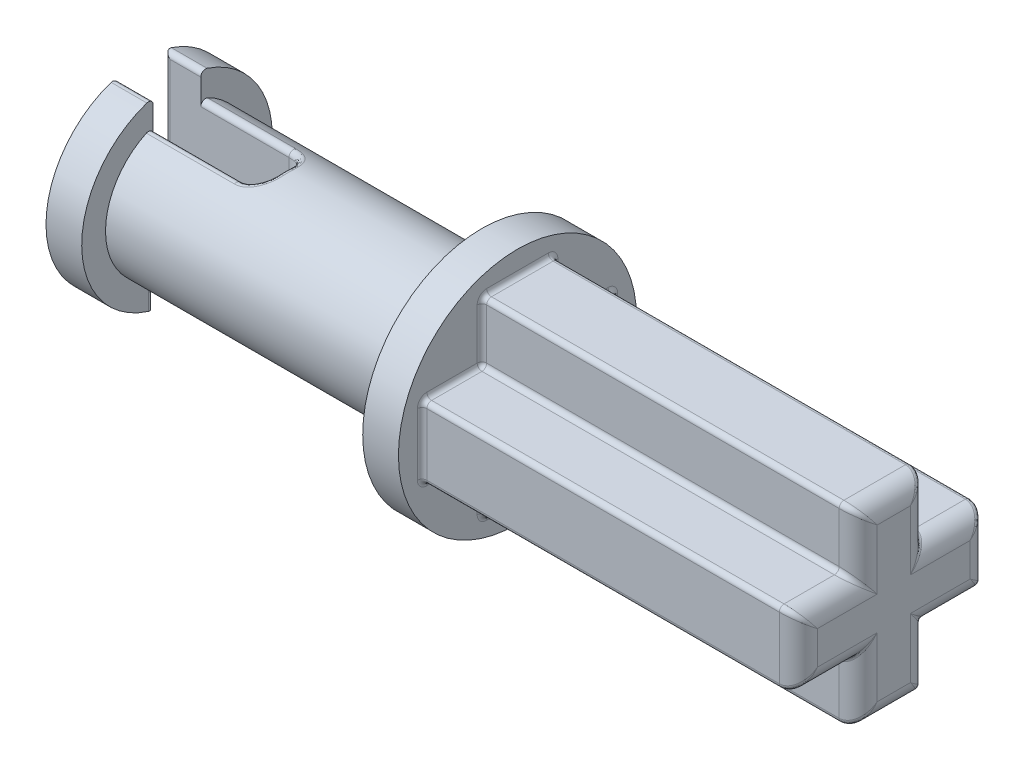
SolidWorks part; units mm, degrees
ref_plane "Front Plane" through (0, 0, 0) normal (0, 0, 1) x (1, 0, 0)
ref_plane "Top Plane" through (0, 0, 0) normal (0, 1, 0) x (1, 0, 0)
ref_plane "Right Plane" through (0, 0, 0) normal (1, 0, 0) x (0, 0, -1)
sketch "CircularBase" plane through (0, 0, 0) normal (0, 0, 1) x (1, 0, 0)
  line L0 (-5.0594, 0) -> (7.0797, 0) construction
  line L1 (0, 0) -> (0, 0.5)
  line L2 (0, 0.5) -> (-2, 0.5)
  line L3 (-2, 0.5) -> (-2, 2)
  line L4 (-2, 2) -> (-1.25, 2)
  line L5 (-1.25, 2) -> (-1.25, 1.5)
  line L6 (-1.25, 1.5) -> (5.15, 1.5)
  line L7 (5.15, 1.5) -> (5.15, 2.5)
  line L8 (5.15, 2.5) -> (5.9, 2.5)
  line L9 (5.9, 2.5) -> (5.9, 0)
  line L11 (0, 0) -> (5.9, 0)
  line L12 (7.0797, 0) -> (14.1483, 0) construction
  dimension "D1" = 0.75
  dimension "D2" = 0.75
  dimension "D3" = 1
  dimension "D4" = 0.5
  dimension "D5" = 1.5
  dimension "D6" = 0.5
  dimension "D7" = 2.5
  dimension "D8" = 2
  dimension "D9" = 5.9
revolve "CircularBaseRevolve" add sketch "CircularBase" angle 360 about L12
ref_plane "BasePlane" through (-2, 0, 0) normal (-1, 0, 0) x (0, 0, 1)
sketch "NotchCutSketc" plane through (-2, 0, 0) normal (-1, 0, 0) x (0, 0, 1)
  line L0 (0, 2) -> (0, -2) construction
  line L1 (-0.5, 0) -> (-0.5, 1.9365)
  line L2 (-0.5, 1.9365) -> (0.5, 1.9365)
  line L3 (-0.5, 0) -> (-0.5, -1.9365)
  line L4 (-0.5, -1.9365) -> (0.5, -1.9365)
  line L5 (0.5, 0) -> (0.5, -1.9365)
  line L6 (0.5, 0) -> (0.5, 1.9365)
  circle A0 centre (0, 0) radius 2 construction
  circle A1 centre (0, 0) radius 0.5 construction
  circle A2 centre (0, 0) radius 0.5 construction
  point P15 (0, -1.9365)
  point P17 (0, 1.9365)
extrude "NotchCut" cut sketch "NotchCutSketc" against normal blind 3
fillet "InsideNotchFillet1" radius 0.4 1 edges at (1, 0, -0.5) type face fillet first side face at (-0.875, 0, -0.5) second side face at (1, 0, 0)
fillet "InsideNotchFillet2" radius 0.4 1 edges at (1, 0, 0.5) type face fillet first side face at (-0.875, 0, 0.5) second side face at (1, 0, 0.2021)
fillet "OutsideNotchFillet" radius 0.1 16 edges at (-2, 0, 0.5) (-2, 0, -0.5) (-0.325, -1.4142, -0.5) (0.915, -1.4594, -0.3465) (1, -1.5, 0) (0.8413, -1.4403, 0.419) (-0.325, 1.4142, 0.5) (0.915, 1.4594, 0.3465) (1, 1.5, 0) (0.8413, 1.4403, -0.419) (-1.625, 1.9365, 0.5) (-1.625, 1.9365, -0.5) (-1.625, -1.9365, -0.5) (-0.325, -1.4142, 0.5) (-0.325, 1.4142, -0.5) (-1.25, -1.6754, 0.5)
ref_plane "TopBasePlane" through (5.9, 0, 0) normal (1, 0, 0) x (0, 0, -1)
sketch "TopCircularBaseExtrudeSketch" plane through (5.9, 0, 0) normal (1, 0, 0) x (0, 0, -1)
  line L0 (0, 2.007) -> (0, -2.007) construction
  line L13 (-2.0033, 0) -> (2.0033, 0) construction
  line L16 (-2.0033, -0.7505) -> (-2.0033, 0.7505)
  line L17 (-2.0033, 0.7505) -> (-0.7468, 0.7505)
  line L18 (0.7468, 2.007) -> (-0.7468, 2.007)
  line L19 (-0.7468, 2.007) -> (-0.7468, 0.7505)
  line L20 (2.0033, -0.7505) -> (2.0033, 0.7505)
  line L21 (2.0033, 0.7505) -> (0.7468, 0.7505)
  line L22 (0.7468, 2.007) -> (0.7468, 0.7505)
  line L23 (2.0033, -0.7505) -> (0.7468, -0.7505)
  line L24 (0.7468, -2.007) -> (0.7468, -0.7505)
  line L25 (-2.0033, -0.7505) -> (-0.7468, -0.7505)
  line L26 (-0.7468, -2.007) -> (-0.7468, -0.7505)
  line L27 (0.7468, -2.007) -> (-0.7468, -2.007)
  point P16 (2.0033, 0)
extrude "TopCircularBaseExtrude" add sketch "TopCircularBaseExtrudeSketch" along normal blind 7.9
fillet "TopCircularBaseFillet" radius 0.4 12 edges at (13.8, 1.3788, 0.7468) (13.8, 1.3788, -0.7468) (13.8, 0.7505, 1.375) (13.8, 0.7505, -1.375) (13.8, 0, -2.0033) (13.8, -0.7505, -1.375) (13.8, -1.3788, -0.7468) (13.8, -2.007, 0) (13.8, 0, 2.0033) (13.8, 2.007, 0) (13.8, -0.7505, 1.375) (13.8, -1.3788, 0.7468)
fillet "TopCircularbaseSideFillet" radius 0.1 36 edges at (5.9, 1.3788, 0.7468) (5.9, -2.007, 0) (5.9, -0.7505, -1.375) (5.9, 0.7505, -1.375) (5.9, 2.007, 0) (5.9, 0.7505, 1.375) (5.9, -0.7505, 1.375) (13.6828, -1.8899, -0.6296) (13.6828, -0.6334, -0.6296) (13.6828, -0.6334, 0.6296) (13.6828, -1.8899, 0.6296) (13.6828, -0.6334, -1.8861) (13.6828, 0.6334, -1.8861) (13.6828, 0.6334, -0.6296) (13.6828, 1.8899, -0.6296) (13.6828, 0.6334, 1.8861) (13.6828, 0.6334, 0.6296) (13.6828, 1.8899, 0.6296) (13.6828, -0.6334, 1.8861) (5.9, -1.3788, -0.7468) (9.65, -2.007, -0.7468) (9.65, -0.7505, -0.7468) (5.9, -1.3788, 0.7468) (9.65, -0.7505, 0.7468) (9.65, -2.007, 0.7468) (5.9, 0, -2.0033) (9.65, -0.7505, -2.0033) (9.65, 0.7505, -2.0033) (5.9, 1.3788, -0.7468) (9.65, 0.7505, -0.7468) (9.65, 2.007, -0.7468) (5.9, 0, 2.0033) (9.65, 0.7505, 2.0033) (9.65, 0.7505, 0.7468) (9.65, 2.007, 0.7468) (9.65, -0.7505, 2.0033)
ref_plane "Plane1" [suppressed] through (0, -2.007, 0) normal (0, -1, 0) x (-1, 0, 0)
sketch "CircularTipSketch" [suppressed] plane through (0, -2.007, 0) normal (0, -1, 0) x (-1, 0, 0)
  line L0 (-6, 2.0033) -> (-6, -2.0033)
  line L1 (-6, -2.0033) -> (-6, -2.5355)
  line L2 (-6, -2.5355) -> (2.115, -2.5355)
  line L3 (2.115, -2.5355) -> (1.9623, 2.8509)
  line L4 (1.9623, 2.8509) -> (-6, 2.7898)
  line L5 (-6, 2.7898) -> (-6, 2.0033)
extrude "CircularTip" [suppressed] cut sketch "CircularTipSketch" against normal through all
ref_plane "Plane2" [suppressed] through (6, 0, 0) normal (-1, 0, 0) x (0, 0, 1)
mirror "Mirror2" [suppressed]
ref_plane "Plane3" [suppressed] through (0, 2.007, 0) normal (0, 1, 0) x (1, 0, 0)
sketch "BaseCutSketch" [suppressed] plane through (0, 2.007, 0) normal (0, 1, 0) x (1, 0, 0)
  line L0 (5.15, 2.5558) -> (5.15, -2.5)
  line L1 (5.15, -2.5) -> (-2.0426, -2.5)
  line L2 (-2.0426, -2.5) -> (-2.0426, 2.5558)
  line L3 (-2.0426, 2.5558) -> (5.15, 2.5558)
extrude "BaseCut" [suppressed] cut sketch "BaseCutSketch" against normal through all contours L3 L2 L1 L0
ref_plane "Plane4" [suppressed] through (13.8, 0, 0) normal (1, 0, 0) x (0, 0, -1)
sketch "NotchCutSketch" [suppressed] plane through (0, 0, 0) normal (0, 1, 0) x (1, 0, 0)
  line L7 (7.7505, 3.747) -> (7.7505, 0)
  line L14 (7.7505, 0) -> (10.818, 0) construction
  line L19 (7.7505, 0) -> (5.15, 0)
  line L20 (5.15, 2.5) -> (5.15, -2.5) construction
  line L21 (5.15, 0) -> (5.15, 4)
  line L22 (5.15, 4) -> (6.4505, 4)
  line L23 (6.4505, 4) -> (6.4505, 3.747)
  line L24 (6.4505, 3.747) -> (7.7505, 3.747)
  point P16 (7.1, 2.25)
  dimension "D1" = 1.3
  dimension "D2" = 4
revolve "CircularEvolveWithNotch" [suppressed] add sketch "NotchCutSketch" angle 360 about L14
ref_plane "Plane5" [suppressed] through (5.15, 0, 0) normal (-1, 0, 0) x (0, 0, 1)
sketch "CrossHoleCutSketch" [suppressed] plane through (5.15, 0, 0) normal (-1, 0, 0) x (0, 0, 1)
  line L0 (-0.8429, 0.8584) -> (-0.8429, 1.9149)
  line L1 (-0.6429, 2.1149) -> (0.6506, 2.1149)
  line L2 (0.8506, 1.9149) -> (0.8506, 0.8584)
  line L3 (0.8506, 0.8584) -> (1.9071, 0.8584)
  line L4 (-1.8994, 0.8584) -> (-0.8429, 0.8584)
  line L5 (-0.8429, -0.8427) -> (-1.8994, -0.8427)
  line L6 (-0.8429, -0.8427) -> (-0.8429, -1.8992)
  line L7 (-0.6429, -2.0992) -> (0.6506, -2.0992)
  line L8 (0.8506, -1.8992) -> (0.8506, -0.8427)
  line L9 (0.8506, -0.8427) -> (1.9071, -0.8427)
  line L10 (2.1071, -0.6427) -> (2.1071, 0.6584)
  line L11 (-2.0994, -0.6427) -> (-2.0994, 0.6584)
  arc A0 (-0.8429, 1.9149) -> (-0.6429, 2.1149) centre (-0.6429, 1.9149) cw
  arc A1 (0.8506, 1.9149) -> (0.6506, 2.1149) centre (0.6506, 1.9149) ccw
  arc A2 (1.9071, 0.8584) -> (2.1071, 0.6584) centre (1.9071, 0.6584) cw
  arc A3 (1.9071, -0.8427) -> (2.1071, -0.6427) centre (1.9071, -0.6427) ccw
  arc A4 (0.8506, -1.8992) -> (0.6506, -2.0992) centre (0.6506, -1.8992) cw
  arc A5 (-0.6429, -2.0992) -> (-0.8429, -1.8992) centre (-0.6429, -1.8992) cw
  arc A6 (-1.8994, -0.8427) -> (-2.0994, -0.6427) centre (-1.8994, -0.6427) cw
  arc A7 (-1.8994, 0.8584) -> (-2.0994, 0.6584) centre (-1.8994, 0.6584) ccw
extrude "CrossHoleCut" [suppressed] cut sketch "CrossHoleCutSketch" against normal through all
ref_plane "Plane11" [suppressed] through (7.7505, 0, 0) normal (1, 0, 0) x (0, 0, -1)
sketch "Sketch16" [suppressed] plane through (7.7505, 0, 0) normal (1, 0, 0) x (0, 0, -1)
  line L1 (0.8429, 0.8584) -> (0.8429, 1.9149)
  line L3 (-0.8506, 0.8584) -> (-1.9071, 0.8584)
  line L4 (-2.1071, 0.6584) -> (-2.1071, -0.6427)
  line L5 (-1.9071, -0.8427) -> (-0.8506, -0.8427)
  line L6 (-0.8506, -0.8427) -> (-0.8506, -1.8992)
  line L7 (0.8429, -1.8992) -> (0.8429, -0.8427)
  line L8 (0.8429, -0.8427) -> (1.8994, -0.8427)
  line L9 (2.0994, -0.6427) -> (2.0994, 0.7075)
  line L10 (0.8429, 0.8584) -> (1.8994, 0.8584)
  line L11 (-0.6506, -2.0992) -> (0.6429, -2.0992)
  line L12 (-0.8506, 0.8584) -> (-0.8506, 1.9149)
  line L13 (-0.6506, 2.1149) -> (0.6429, 2.1149)
  circle A0 centre (0, 0) radius 4
  arc A1 (-1.9071, -0.8427) -> (-2.1071, -0.6427) centre (-1.9071, -0.6427) cw
  arc A2 (-2.1071, 0.6584) -> (-1.9071, 0.8584) centre (-1.9071, 0.6584) cw
  arc A6 (1.8994, 0.8584) -> (2.0994, 0.7075) centre (1.8994, 0.6504) cw
  arc A7 (2.0994, -0.6427) -> (1.8994, -0.8427) centre (1.8994, -0.6427) cw
  arc A8 (0.8429, -1.8992) -> (0.6429, -2.0992) centre (0.6429, -1.8992) cw
  arc A9 (-0.8506, -1.8992) -> (-0.6506, -2.0992) centre (-0.6506, -1.8992) ccw
  arc A10 (-0.8506, 1.9149) -> (-0.6506, 2.1149) centre (-0.6506, 1.9149) cw
  arc A11 (0.8429, 1.9149) -> (0.6429, 2.1149) centre (0.6429, 1.9149) ccw
extrude "CircularCrossHolwCircle" [suppressed] add sketch "Sketch16" along normal blind 1.25
fillet "EdgesFillet" [suppressed] radius 0.1
fillet "Fillet2" [suppressed] radius 0.1
ref_plane "Plane6" [suppressed] through (0, 0, -2.0033) normal (0, 0, -1) x (-1, 0, 0)
sketch "Sketch1" [suppressed] plane through (0, 0, -2.0033) normal (0, 0, -1) x (-1, 0, 0)
  line L0 (-5.9, 2.5) -> (-5.9, -2.5)
  line L1 (-5.9, 2.5) -> (-5.9, -2.5) construction
  line L2 (-5.9, -2.5) -> (-13.8486, -2.5)
  line L3 (-13.8486, -2.5) -> (-13.8486, 2.5)
  line L4 (-13.8486, 2.5) -> (-5.9, 2.5)
extrude "RemovedMaterial" [suppressed] cut sketch "Sketch1" against normal through all
sketch "Sketch2" [suppressed] plane through (0, 0, -2.0033) normal (0, 0, -1) x (-1, 0, 0)
  line L1 (-11.5273, 0) -> (-12.3621, 0) construction
  line L2 (-5.15, 4.2) -> (-5.15, 0.25)
  line L3 (-5.15, 4.2) -> (-8.341, 4.2)
  line L4 (-8.341, 1.2482) -> (-11.5214, 1.2482)
  line L6 (-11.5214, 1.2482) -> (-11.5214, 0.25)
  line L8 (-8.341, 4.2) -> (-8.341, 1.2482)
  line L10 (-5.15, -2.5) -> (-5.15, 2.5) construction
  line L11 (-5.15, 0.25) -> (-11.5214, 0.25)
  dimension "D1" = 3.95
revolve "Revolve2" [suppressed] add sketch "Sketch2" angle 360 about L1
ref_plane "Plane8" [suppressed] through (5.9, 0, 0) normal (1, 0, 0) x (0, 0, -1)
sketch "Sketch13" [suppressed] plane through (5.9, 0, 0) normal (1, 0, 0) x (0, 0, -1)
  arc A0 (-1.8412, 1.6911) -> (-1.8412, -1.6911) centre (0, 0) ccw
  arc A2 (-1.8412, 1.6911) -> (-1.8412, -1.6911) centre (2.0033, 0) ccw
  dimension "D1" = 2.5
extrude "RemovedMaterial2" [suppressed] cut sketch "Sketch13" against normal through all
sketch "Sketch14" [suppressed] plane through (5.9, 0, 0) normal (1, 0, 0) x (0, 0, -1)
  line L0 (2.0033, -0.25) -> (2.0033, 0.25) construction
  circle A0 centre (2.0033, 0) radius 0.2516
ref_plane "ShellPlane" [suppressed] through (5.15, 0, 0) normal (-1, 0, 0) x (0, 0, 1)
sketch "ShellSketch" [suppressed] plane through (5.15, 0, 0) normal (-1, 0, 0) x (0, 0, 1)
  circle A0 centre (-2.0033, 0) radius 1.9017
extrude "ShellFeature" [suppressed] cut sketch "ShellSketch" against normal blind 1.6
ref_plane "Plane13" [suppressed] through (8.341, 0, 0) normal (1, 0, 0) x (0, 0, -1)
sketch "RemoveMaterialSketch3" [suppressed] plane through (8.341, 0, 0) normal (1, 0, 0) x (0, 0, -1)
  circle A0 centre (2.0033, 0) radius 1.2482
extrude "RemoveMaterial3" [suppressed] cut sketch "RemoveMaterialSketch3" along normal through all
sketch "Sketch21" [suppressed] plane through (8.341, 0, 0) normal (1, 0, 0) x (0, 0, -1)
  circle A0 centre (2.0033, 0) radius 2.4
  circle A1 centre (2.0033, 0) radius 2
  dimension "D1" = 4.8
  dimension "D2" = 4
extrude "CylindereExtrudeVertical" [suppressed] add sketch "Sketch21" along normal blind 2
sketch "ThroughHoleSketch" [suppressed] plane through (8.341, 0, 0) normal (1, 0, 0) x (0, 0, -1)
  circle A0 centre (2.0033, 0) radius 2
extrude "ThroughHole" [suppressed] cut sketch "ThroughHoleSketch" against normal through all
ref_plane "Plane14" [suppressed] through (5.15, 0, 0) normal (-1, 0, 0) x (0, 0, 1)
sketch "Sketch23" [suppressed] plane through (5.15, 0, 0) normal (-1, 0, 0) x (0, 0, 1)
  circle A0 centre (-2.0033, 0) radius 2.4
  dimension "D1" = 4.8
extrude "Cut-Extrude6" [suppressed] cut sketch "Sketch23" against normal blind 1.6
ref_plane "BisectingPlane" [suppressed] through (6.7455, 0, 0) normal (1, 0, 0) x (0, 0, -1)
sketch "Sketch24" [suppressed] plane through (6.7455, 0, 0) normal (1, 0, 0) x (0, 0, -1)
  line L0 (2.0033, 0) -> (2.0033, 3.4935) construction
  line L2 (3.5835, 3.5518) -> (3.5835, 8.4935)
  line L4 (2.0033, 9.1481) -> (2.0033, 10.1942) construction
  line L5 (2.0033, 9.1481) -> (2.0033, 3.5518)
  line L6 (2.0033, 3.5518) -> (3.5835, 3.5518)
  arc A0 (2.0033, 9.1481) -> (3.5835, 8.4935) centre (2.0033, 6.9132) cw
  point P7 (2.0033, 3.4935)
revolve "CylinderRevolve" [suppressed] add sketch "Sketch24" angle 360 about L4
sketch "Sketch25" [suppressed] plane through (6.7455, 0, 0) normal (1, 0, 0) x (0, 0, -1)
  line L0 (2.0033, 4.2) -> (2.0033, 10.2085) construction
  line L1 (3.5835, 8.4935) -> (0.423, 8.4935) construction
  arc A0 (3.5835, 3.8914) -> (0.423, 3.8914) centre (2.0033, 0) ccw construction
  circle A1 centre (2.0033, 8.4935) radius 1.5349
extrude "Boss-Extrude3" [suppressed] add sketch "Sketch25" against normal blind 7
sketch "Sketch27" [suppressed] plane through (6.7455, 0, 0) normal (1, 0, 0) x (0, 0, -1)
  line L0 (2.0033, 8.4935) -> (2.0033, 10.0284)
  line L1 (3.5835, 8.4935) -> (0.423, 8.4935) construction
  line L2 (2.0033, 8.4935) -> (0.423, 8.4935)
  line L3 (2.0033, 10.379) -> (2.0033, 10.0284) construction
  arc A0 (3.5376, 8.5382) -> (0.469, 8.5382) centre (2.0033, 8.4935) ccw construction
  arc A1 (0.423, 8.4935) -> (2.0033, 10.0284) centre (1.9586, 8.4935) cw
revolve "Revolve4" [suppressed] add sketch "Sketch27" angle 360 about L3
ref_plane "Plane17" [suppressed] through (-0.2545, 0, 0) normal (-1, 0, 0) x (0, 0, 1)
sketch "Sketch28" [suppressed] plane through (-0.2545, 0, 0) normal (-1, 0, 0) x (0, 0, 1)
  line L0 (-2.0033, 10.0284) -> (-2.0033, 6.9586) construction
  line L1 (-3.5382, 8.4935) -> (-0.4683, 8.4935) construction
  arc A0 (-3.5382, 8.4935) -> (-0.4683, 8.4935) centre (-2.0033, 8.4935) ccw construction
  circle A1 centre (-2.0033, 8.4935) radius 0.5026
extrude "SmallHoleInCylinder" [suppressed] cut sketch "Sketch28" against normal blind 3
ref_plane "Plane18" [suppressed] through (21.6, 0, 0) normal (1, 0, 0) x (0, 0, -1)
sketch "Sketch29" [suppressed] plane through (21.6, 0, 0) normal (1, 0, 0) x (0, 0, -1)
  line L7 (0.776, -2.675) -> (-1.1035, -2.675) construction
  line L8 (1.0733, 2.6336) -> (1.0733, 1.1385) construction
  line L9 (-1.0733, 2.6336) -> (-1.0733, 1.1201) construction
  line L10 (-1.0733, 2.6336) -> (1.0733, 2.652)
  line L11 (1.0733, 2.652) -> (1.0733, 1.1385)
  line L12 (1.0733, 1.1385) -> (2.4478, 1.1385)
  line L13 (2.4478, 1.1385) -> (2.4478, -1.1615)
  line L14 (2.4478, -1.1615) -> (1.0733, -1.1615)
  line L16 (1.0733, -2.675) -> (-1.1035, -2.675)
  line L17 (-1.1035, -2.675) -> (-1.1035, -1.1615)
  line L18 (-1.1035, -1.1615) -> (-2.4478, -1.1615)
  line L19 (-2.4478, -1.1615) -> (-2.4478, 1.1201)
  line L20 (-2.4478, 1.1201) -> (-1.0733, 1.1201)
  line L21 (-1.0733, 1.1201) -> (-1.0733, 2.6336)
  line L23 (1.0733, -1.1615) -> (1.0733, -2.675)
  circle A0 centre (0, 0) radius 3.45
  dimension "D1" = 6.9
  dimension "D3" = 0.775
  dimension "D2" = 2.3
extrude "Boss-Extrude5" [suppressed] add sketch "Sketch29" along normal blind 15.8 separate body
ref_plane "Plane19" [suppressed] through (0, 0, -2.0033) normal (0, 0, -1) x (-1, 0, 0)
sketch "Sketch30" [suppressed] plane through (0, 0, -2.0033) normal (0, 0, -1) x (-1, 0, 0)
  line L0 (-21.6, 3.4921) -> (-21.6, -3.45)
  line L1 (-21.6, 3.1156) -> (-21.6, -3.1156) construction
  line L2 (-21.6, -3.45) -> (-21.6, 3.45) construction
  line L3 (-21.6, -3.45) -> (9.8373, -3.45)
  line L4 (9.8373, -3.45) -> (9.8373, 3.4921)
  line L5 (9.8373, 3.4921) -> (-21.6, 3.4921)
extrude "Cut-Extrude7" [suppressed] cut sketch "Sketch30" against normal through all
sketch "Sketch31" [suppressed] plane through (21.6, 0, 0) normal (1, 0, 0) x (0, 0, -1)
  line L0 (0, -3.485) -> (0, 0) construction
  line L1 (0, 0) -> (2.3068, 0) construction
  line L3 (-2.6444, 2.1051) -> (-2.7334, 2.1051)
  line L5 (-2.6444, -2.1051) -> (-2.7334, -2.1051)
  line L7 (2.6444, -2.1051) -> (2.7334, -2.1051)
  line L8 (2.6444, 2.1051) -> (2.7334, 2.1051)
  circle A0 centre (0, 0) radius 3.45 construction
  arc A1 (-2.7334, 2.1051) -> (-1.8163, 2.9332) centre (-0.5362, 0.5938) cw
  arc A2 (-2.7334, -2.1051) -> (-1.8163, -2.9332) centre (-0.5362, -0.5938) ccw
  arc A3 (2.7334, -2.1051) -> (1.8163, -2.9332) centre (0.5362, -0.5938) cw
  arc A4 (2.7334, 2.1051) -> (1.8163, 2.9332) centre (0.5362, 0.5938) ccw
  arc A5 (-2.6444, 2.1051) -> (-1.8163, 2.9332) centre (-2.6889, 2.9777) ccw
  arc A6 (2.6444, 2.1051) -> (1.8163, 2.9332) centre (2.6889, 2.9777) cw
  arc A7 (-2.6444, -2.1051) -> (-1.8163, -2.9332) centre (-2.6889, -2.9777) cw
  arc A8 (2.6444, -2.1051) -> (1.8163, -2.9332) centre (2.6889, -2.9777) ccw
extrude "Cut-Extrude8" [suppressed] cut sketch "Sketch31" along normal through all
fillet "Fillet3" [suppressed] radius 0.4
